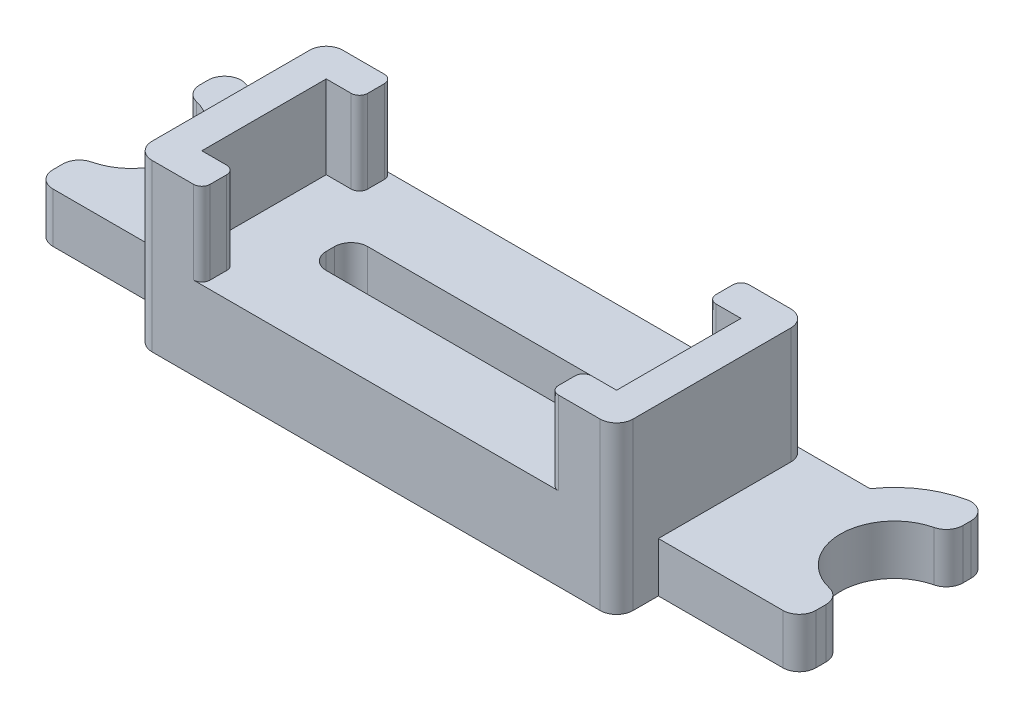
SolidWorks part; units mm, degrees
material "ABS"
ref_plane "Front Plane" through (0, 0, 0) normal (0, 0, 1) x (1, 0, 0)
ref_plane "Top Plane" through (0, 0, 0) normal (0, 1, 0) x (1, 0, 0)
ref_plane "Right Plane" through (0, 0, 0) normal (1, 0, 0) x (0, 0, -1)
sketch "Sketch1" plane through (0, 0, 0) normal (0, 1, 0) x (1, 0, 0)
  line L0 (0, 0) -> (0, 40.2509) construction
  line L1 (0, 0) -> (-23, 0) construction
  line L2 (-29.9073, -3.73) -> (0, -3.73) construction
  line L3 (-23, 3.25) -> (-23, 0) construction
  line L4 (-23, -3.25) -> (-23, -5.73)
  line L5 (-23, 3.25) -> (-23, 5.73)
  line L6 (-23, 3.25) -> (0, 3.25) construction
  line L7 (-23, -5.73) -> (-14.5, -5.73)
  line L8 (-14.5, -5.73) -> (-14.5, -8.25)
  line L9 (23, 3.25) -> (23, 5.73)
  line L10 (23, -3.25) -> (23, -5.73)
  line L11 (23, -5.73) -> (14.5, -5.73)
  line L12 (14.5, -5.73) -> (14.5, -8.25)
  line L13 (-18.2808, 3.25) -> (18.2808, 3.25)
  line L14 (-14.5, -8.25) -> (14.5, -8.25)
  circle A0 centre (-23, 0) radius 3.25 construction
  arc A1 (-23, -3.25) -> (-23, 3.25) centre (-23, 0) ccw
  arc A2 (-23, 5.73) -> (-18.2808, 3.25) centre (-23, 0) cw
  arc A3 (23, 5.73) -> (18.2808, 3.25) centre (23, 0) ccw
  arc A4 (23, -3.25) -> (23, 3.25) centre (23, 0) cw
  dimension "D1" = 6.5
  dimension "D2" = 46
  dimension "D3" = 3.73
  dimension "D4" = 2
  dimension "D5" = 29
  dimension "D6" = 11.5
extrude "Main Body" add sketch "Sketch1" along normal blind 3
sketch "Sketch2" plane through (0, 3, 0) normal (0, 1, 0) x (1, 0, 0)
  line L0 (18.2808, 3.25) -> (-18.2808, 3.25) construction
  line L1 (-14.5, -8.25) -> (14.5, -8.25)
  line L2 (-14.5, -8.25) -> (-14.5, 3.25)
  line L3 (-14.5, 3.25) -> (14.5, 3.25)
  line L4 (14.5, -8.25) -> (14.5, 3.25)
extrude "Fan Offset" add sketch "Sketch2" along normal offset from surface (2 mm away) 5 up to face at (0, 0, 1.4497)
sketch "Sketch3" plane through (0, 5, 0) normal (0, 1, 0) x (1, 0, 0)
  line L0 (0, 3.25) -> (0, -8.25) construction
  line L1 (14.5, 3.25) -> (-14.5, 3.25) construction
  line L2 (-14.5, -8.25) -> (14.5, -8.25) construction
  line L3 (-10.5, 3.25) -> (-14.5, 3.25)
  line L4 (-14.5, 3.25) -> (-14.5, -8.25)
  line L5 (-14.5, -8.25) -> (-10.5, -8.25)
  line L6 (-10.5, -8.25) -> (-10.5, -6.25)
  line L7 (-10.5, -6.25) -> (-12.5, -6.25)
  line L8 (-12.5, -6.25) -> (-12.5, 1.25)
  line L9 (-12.5, 1.25) -> (-10.5, 1.25)
  line L10 (-10.5, 1.25) -> (-10.5, 3.25)
  line L11 (-12.5, -2.5) -> (-14.5, -2.5) construction
  line L12 (12.5, -6.25) -> (12.5, 1.25)
  line L13 (10.5, -6.25) -> (12.5, -6.25)
  line L14 (10.5, -8.25) -> (10.5, -6.25)
  line L15 (14.5, -8.25) -> (10.5, -8.25)
  line L16 (14.5, 3.25) -> (14.5, -8.25)
  line L17 (10.5, 3.25) -> (14.5, 3.25)
  line L18 (10.5, 1.25) -> (10.5, 3.25)
  line L19 (12.5, 1.25) -> (10.5, 1.25)
  dimension "D1" = 2
  dimension "D2" = 2
extrude "Fan Frame" add sketch "Sketch3" along normal blind 5
sketch "Sketch4" plane through (0, 5, 0) normal (0, 1, 0) x (1, 0, 0)
  line L0 (0, 3.25) -> (0, -8.25) construction
  line L1 (10.5, 3.25) -> (-10.5, 3.25) construction
  line L2 (-10.5, -8.25) -> (10.5, -8.25) construction
  line L3 (-12.5, -2.5) -> (12.5, -2.5) construction
  line L4 (-12.5, -6.25) -> (-12.5, 1.25) construction
  line L5 (12.5, 1.25) -> (12.5, -6.25) construction
  line L6 (-12.5, 1.25) -> (-10.5, 1.25) construction
  line L7 (-8.5, -1.25) -> (8.5, -1.25)
  line L8 (-8.5, -1.25) -> (-8.5, -3.75)
  line L9 (-8.5, -3.75) -> (8.5, -3.75)
  line L10 (8.5, -1.25) -> (8.5, -3.75)
  dimension "D1" = 4
  dimension "D2" = 2.5
extrude "Speed Hole" cut sketch "Sketch4" against normal through all
fillet "Contouring" radius 1 16 edges at (14.5, 5, 8.25) (-14.5, 5, 8.25) (23, 1.5, 5.73) (23, 1.5, 3.25) (23, 1.5, -3.25) (23, 1.5, -5.73) (-23, 1.5, 5.73) (-23, 1.5, 3.25) (-23, 1.5, -3.25) (-23, 1.5, -5.73) (-8.5, 2.5, 1.25) (-8.5, 2.5, 3.75) (8.5, 2.5, 3.75) (8.5, 2.5, 1.25)
fillet "Fit Clearance - Contouring" radius 0.5 8 edges at (10.5, 7.5, -3.25) (-10.5, 7.5, 6.25) (10.5, 7.5, 8.25) (10.5, 7.5, 6.25) (10.5, 7.5, -1.25) (-10.5, 7.5, -1.25)
ref_point "Point1"
